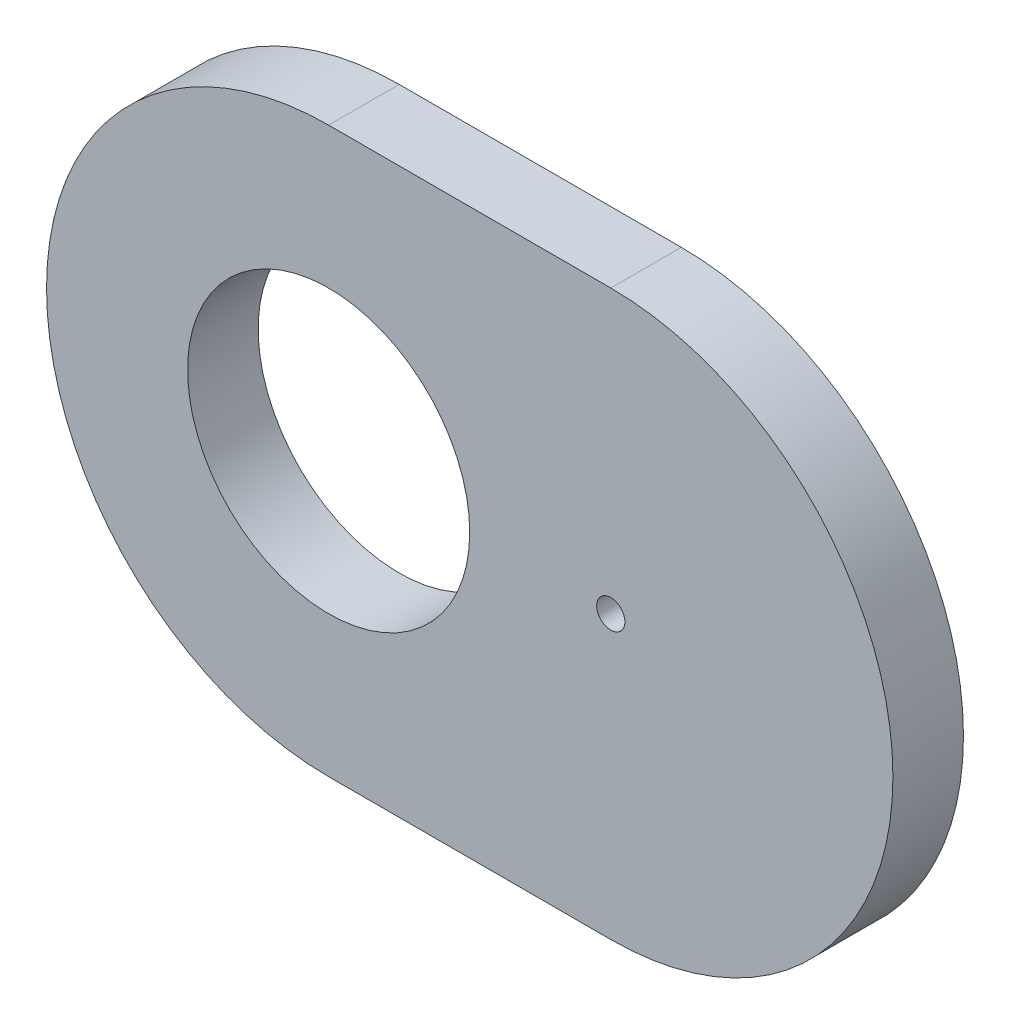
SolidWorks part; units mm, degrees
ref_plane "Front Plane" through (0, 0, 0) normal (0, 0, 1) x (1, 0, 0)
ref_plane "Top Plane" through (0, 0, 0) normal (0, 1, 0) x (1, 0, 0)
ref_plane "Right Plane" through (0, 0, 0) normal (1, 0, 0) x (0, 0, -1)
sketch "Sketch3" plane through (0, 0, 0) normal (0, 0, 1) x (1, 0, 0)
  line L0 (-1.0348, -48.4654) -> (24.3652, -48.4654) construction
  line L1 (-1.0348, -23.0654) -> (24.3652, -23.0654)
  line L2 (-1.0348, -73.8654) -> (24.3652, -73.8654)
  arc A0 (-1.0348, -23.0654) -> (-1.0348, -73.8654) centre (-1.0348, -48.4654) ccw
  arc A1 (24.3652, -73.8654) -> (24.3652, -23.0654) centre (24.3652, -48.4654) ccw
  circle A2 centre (-1.0348, -48.4654) radius 12.7
  circle A3 centre (24.3652, -48.4654) radius 1.27 construction
  circle A4 centre (24.3652, -48.4654) radius 1.27
  point P2 (11.6652, -48.4654)
  point P11 (49.7652, -48.4654)
  point P12 (-26.4348, -48.4654)
  dimension "D3" = 25.4
  dimension "D4" = 2.54
  dimension "D1" = 50.8
  dimension "D2" = 76.2
extrude "Boss-Extrude1" add sketch "Sketch3" along normal blind 6.35 contours L1 A1 L2 A0
extrude "Cut-Extrude1" cut sketch "Sketch3<6>" along normal blind 6.35 contours A2
sketch "Sketch3<6>" plane through (0, 0, 0) normal (0, 0, 1) x (1, 0, 0) same geometry as "Sketch3"
extrude "Cut-Extrude5" cut sketch "Sketch3<9>" along normal blind 6.35 contours A4
sketch "Sketch3<9>" plane through (0, 0, 0) normal (0, 0, 1) x (1, 0, 0) same geometry as "Sketch3"
equation "\"h\"= 3in"
equation "\"dshaft\"= 1in"
equation "\"wi\"= 2in"
equation "\"Ys\"= 36000"
equation "\"r2\"= 0.1in"
equation "\"Force\"= 275"
equation "\"Max_deflection\"= 0.005in"
equation "\"t\"= 0.25in"
equation "\"D1@Sketch3\"=\"wi\""
equation "\"D2@Sketch3\"=\"h\""
equation "\"D3@Sketch3\"=\"dshaft\""
equation "\"D4@Sketch3\"=\"r2\""
equation "\"D1@Boss-Extrude1\"=\"t\""
